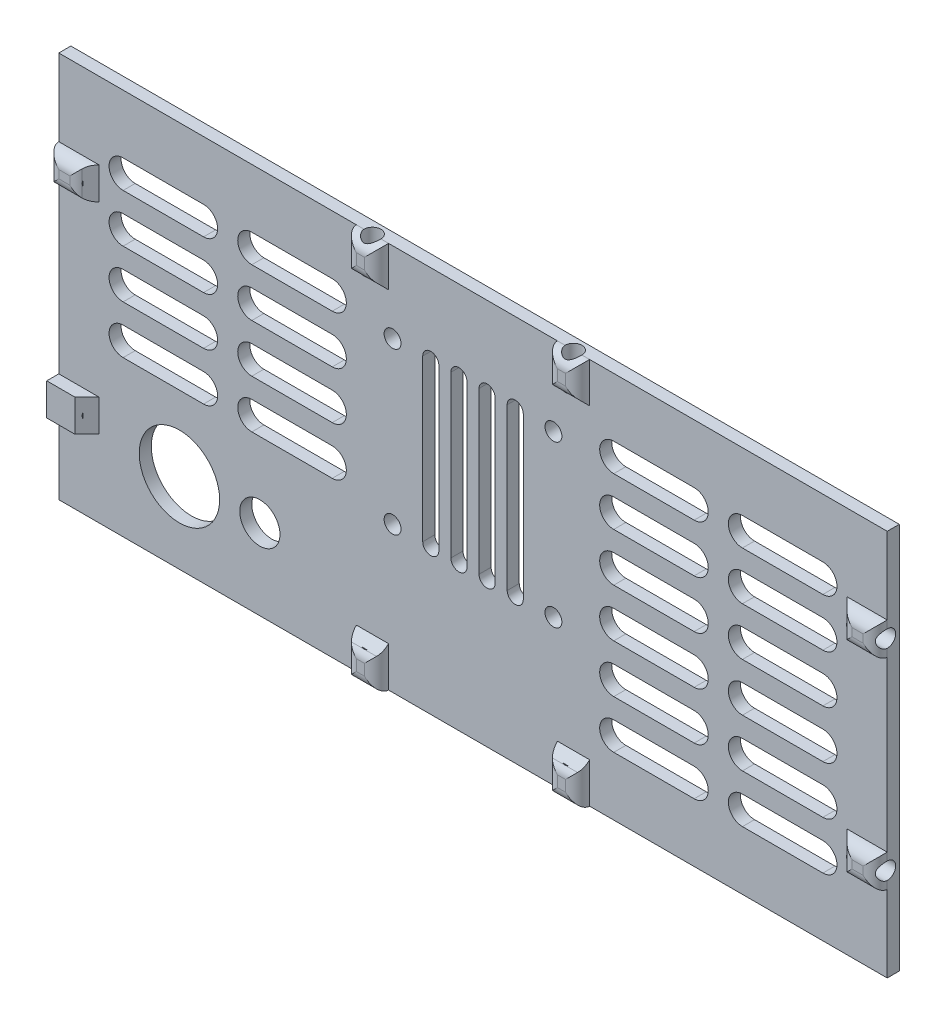
SolidWorks part; units mm, degrees
ref_plane "Front Plane" through (0, 0, 0) normal (1, 0, 0) x (0, 1, 0)
ref_plane "Top Plane" through (0, 0, 0) normal (0, 0, 1) x (0, 1, 0)
ref_plane "Right Plane" through (0, 0, 0) normal (0, 1, 0) x (-1, 0, 0)
sketch "Sketch1" plane through (0, 0, 0) normal (0, 0, 1) x (0, 1, 0)
  line L0 (36.2019, 113.5) -> (76.2019, 113.5) construction
  line L1 (0, 0) -> (96.2019, 0)
  line L2 (0, 0) -> (0, 206)
  line L3 (0, 206) -> (96.2019, 206)
  line L4 (96.2019, 0) -> (96.2019, 206)
  line L5 (36.2019, 115.5) -> (76.2019, 115.5)
  line L6 (36.2019, 111.5) -> (76.2019, 111.5)
  line L7 (36.2019, 106.5) -> (76.2019, 106.5) construction
  line L8 (36.2019, 108.5) -> (76.2019, 108.5)
  line L9 (36.2019, 104.5) -> (76.2019, 104.5)
  line L10 (36.2019, 99.5) -> (76.2019, 99.5) construction
  line L11 (36.2019, 101.5) -> (76.2019, 101.5)
  line L12 (36.2019, 97.5) -> (76.2019, 97.5)
  line L13 (36.2019, 92.5) -> (76.2019, 92.5) construction
  line L14 (36.2019, 94.5) -> (76.2019, 94.5)
  line L15 (36.2019, 90.5) -> (76.2019, 90.5)
  line L16 (6, 200) -> (90.2019, 200) construction
  line L17 (90.2019, 6) -> (90.2019, 200) construction
  line L18 (6, 6) -> (90.2019, 6) construction
  line L19 (6, 6) -> (6, 200) construction
  line L20 (6.101, 68) -> (6.101, 48) construction
  line L21 (9.601, 68) -> (9.601, 48) construction
  line L22 (96.2019, 103) -> (0, 103) construction
  line L23 (2.601, 68) -> (2.601, 48) construction
  line L24 (18.101, 68) -> (18.101, 48) construction
  line L25 (21.601, 68) -> (21.601, 48)
  line L26 (14.601, 68) -> (14.601, 48)
  line L27 (30.1009, 68) -> (30.1009, 48) construction
  line L28 (33.6009, 68) -> (33.601, 48)
  line L29 (26.6009, 68) -> (26.6009, 48)
  line L30 (42.101, 68) -> (42.1009, 48) construction
  line L31 (45.601, 68) -> (45.601, 48)
  line L32 (38.601, 68) -> (38.601, 48)
  line L33 (54.1009, 68) -> (54.1009, 48) construction
  line L34 (57.6009, 68) -> (57.6009, 48)
  line L35 (50.6009, 68) -> (50.6009, 48)
  line L36 (66.1009, 68) -> (66.1009, 48) construction
  line L37 (69.6009, 68) -> (69.6009, 48)
  line L38 (62.6009, 68) -> (62.6009, 48)
  line L39 (78.1009, 68) -> (78.1009, 48) construction
  line L40 (81.6009, 68) -> (81.6009, 48)
  line L41 (74.6009, 68) -> (74.6009, 48)
  line L42 (90.1009, 68) -> (90.1009, 48) construction
  line L43 (93.6009, 68) -> (93.6009, 48) construction
  line L44 (86.6009, 68) -> (86.6009, 48) construction
  line L45 (48.1009, 200) -> (48.1009, 6) construction
  line L46 (6, 42) -> (90.2019, 42) construction
  line L47 (6.101, 16) -> (6.101, 36) construction
  line L48 (9.601, 16) -> (9.601, 36) construction
  line L49 (2.601, 16) -> (2.601, 36) construction
  line L50 (18.101, 16) -> (18.101, 36) construction
  line L51 (21.601, 16) -> (21.601, 36)
  line L52 (14.601, 16) -> (14.601, 36)
  line L53 (30.1009, 16) -> (30.1009, 36) construction
  line L54 (33.6009, 16) -> (33.601, 36)
  line L55 (26.6009, 16) -> (26.6009, 36)
  line L56 (42.101, 16) -> (42.1009, 36) construction
  line L57 (45.601, 16) -> (45.601, 36)
  line L58 (38.601, 16) -> (38.601, 36)
  line L59 (54.1009, 16) -> (54.1009, 36) construction
  line L60 (57.6009, 16) -> (57.6009, 36)
  line L61 (50.6009, 16) -> (50.6009, 36)
  line L62 (66.1009, 16) -> (66.1009, 36) construction
  line L63 (69.6009, 16) -> (69.6009, 36)
  line L64 (62.6009, 16) -> (62.6009, 36)
  line L65 (78.1009, 16) -> (78.1009, 36) construction
  line L66 (81.6009, 16) -> (81.6009, 36)
  line L67 (74.6009, 16) -> (74.6009, 36)
  line L68 (90.1009, 16) -> (90.1009, 36) construction
  line L69 (93.6009, 16) -> (93.6009, 36) construction
  line L70 (86.6009, 16) -> (86.6009, 36) construction
  line L71 (6.101, 138) -> (6.101, 158) construction
  line L72 (9.601, 138) -> (9.601, 158) construction
  line L73 (2.601, 138) -> (2.601, 158) construction
  line L74 (18.101, 138) -> (18.101, 158) construction
  line L75 (21.601, 138) -> (21.601, 158) construction
  line L76 (14.601, 138) -> (14.601, 158) construction
  line L77 (30.1009, 138) -> (30.1009, 158) construction
  line L78 (33.6009, 138) -> (33.601, 158) construction
  line L79 (26.6009, 138) -> (26.6009, 158) construction
  line L80 (42.101, 138) -> (42.1009, 158) construction
  line L81 (45.601, 138) -> (45.601, 158)
  line L82 (38.601, 138) -> (38.601, 158)
  line L83 (54.1009, 138) -> (54.1009, 158) construction
  line L84 (57.6009, 138) -> (57.6009, 158)
  line L85 (50.6009, 138) -> (50.6009, 158)
  line L86 (66.1009, 138) -> (66.1009, 158) construction
  line L87 (69.6009, 138) -> (69.6009, 158)
  line L88 (62.6009, 138) -> (62.6009, 158)
  line L89 (78.1009, 138) -> (78.1009, 158) construction
  line L90 (81.6009, 138) -> (81.6009, 158)
  line L91 (74.6009, 138) -> (74.6009, 158)
  line L92 (90.1009, 138) -> (90.1009, 158) construction
  line L93 (93.6009, 138) -> (93.6009, 158) construction
  line L94 (86.6009, 138) -> (86.6009, 158) construction
  line L95 (6.101, 190) -> (6.101, 170) construction
  line L96 (9.601, 190) -> (9.601, 170) construction
  line L97 (2.601, 190) -> (2.601, 170) construction
  line L98 (18.101, 190) -> (18.101, 170) construction
  line L99 (21.601, 190) -> (21.601, 170) construction
  line L100 (14.601, 190) -> (14.601, 170) construction
  line L101 (30.1009, 190) -> (30.1009, 170) construction
  line L102 (33.6009, 190) -> (33.601, 170) construction
  line L103 (26.6009, 190) -> (26.6009, 170) construction
  line L104 (42.101, 190) -> (42.1009, 170) construction
  line L105 (45.601, 190) -> (45.601, 170)
  line L106 (38.601, 190) -> (38.601, 170)
  line L107 (54.1009, 190) -> (54.1009, 170) construction
  line L108 (57.6009, 190) -> (57.6009, 170)
  line L109 (50.6009, 190) -> (50.6009, 170)
  line L110 (66.1009, 190) -> (66.1009, 170) construction
  line L111 (69.6009, 190) -> (69.6009, 170)
  line L112 (62.6009, 190) -> (62.6009, 170)
  line L113 (78.1009, 190) -> (78.1009, 170) construction
  line L114 (81.6009, 190) -> (81.6009, 170)
  line L115 (74.6009, 190) -> (74.6009, 170)
  line L116 (90.1009, 190) -> (90.1009, 170) construction
  line L117 (93.6009, 190) -> (93.6009, 170) construction
  line L118 (86.6009, 190) -> (86.6009, 170) construction
  arc A0 (36.2019, 115.5) -> (36.2019, 111.5) centre (36.2019, 113.5) ccw
  arc A1 (76.2019, 111.5) -> (76.2019, 115.5) centre (76.2019, 113.5) ccw
  arc A2 (36.2019, 108.5) -> (36.2019, 104.5) centre (36.2019, 106.5) ccw
  arc A3 (76.2019, 104.5) -> (76.2019, 108.5) centre (76.2019, 106.5) ccw
  arc A4 (36.2019, 101.5) -> (36.2019, 97.5) centre (36.2019, 99.5) ccw
  arc A5 (76.2019, 97.5) -> (76.2019, 101.5) centre (76.2019, 99.5) ccw
  arc A6 (36.2019, 94.5) -> (36.2019, 90.5) centre (36.2019, 92.5) ccw
  arc A7 (76.2019, 90.5) -> (76.2019, 94.5) centre (76.2019, 92.5) ccw
  circle A8 centre (36.2019, 123) radius 2.1
  circle A9 centre (76.2019, 123) radius 2.1
  circle A10 centre (36.2019, 83) radius 2.1
  circle A11 centre (76.2019, 83) radius 2.1
  circle A12 centre (20, 176) radius 10
  circle A13 centre (20, 156) radius 5
  arc A14 (9.601, 68) -> (2.601, 68) centre (6.101, 68) ccw construction
  arc A15 (2.601, 48) -> (9.601, 48) centre (6.101, 48) ccw construction
  arc A16 (21.601, 68) -> (14.601, 68) centre (18.101, 68) ccw
  arc A17 (14.601, 48) -> (21.601, 48) centre (18.101, 48) ccw
  arc A18 (33.6009, 68) -> (26.6009, 68) centre (30.1009, 68) ccw
  arc A19 (26.6009, 48) -> (33.601, 48) centre (30.1009, 48) ccw
  arc A20 (45.601, 68) -> (38.601, 68) centre (42.101, 68) ccw
  arc A21 (38.601, 48) -> (45.601, 48) centre (42.1009, 48) ccw
  arc A22 (57.6009, 68) -> (50.6009, 68) centre (54.1009, 68) ccw
  arc A23 (50.6009, 48) -> (57.6009, 48) centre (54.1009, 48) ccw
  arc A24 (69.6009, 68) -> (62.6009, 68) centre (66.1009, 68) ccw
  arc A25 (62.6009, 48) -> (69.6009, 48) centre (66.1009, 48) ccw
  arc A26 (81.6009, 68) -> (74.6009, 68) centre (78.1009, 68) ccw
  arc A27 (74.6009, 48) -> (81.6009, 48) centre (78.1009, 48) ccw
  arc A28 (93.6009, 68) -> (86.6009, 68) centre (90.1009, 68) ccw construction
  arc A29 (86.6009, 48) -> (93.6009, 48) centre (90.1009, 48) ccw construction
  arc A30 (9.601, 16) -> (2.601, 16) centre (6.101, 16) cw construction
  arc A31 (2.601, 36) -> (9.601, 36) centre (6.101, 36) cw construction
  arc A32 (21.601, 16) -> (14.601, 16) centre (18.101, 16) cw
  arc A33 (14.601, 36) -> (21.601, 36) centre (18.101, 36) cw
  arc A34 (33.6009, 16) -> (26.6009, 16) centre (30.1009, 16) cw
  arc A35 (26.6009, 36) -> (33.601, 36) centre (30.1009, 36) cw
  arc A36 (45.601, 16) -> (38.601, 16) centre (42.101, 16) cw
  arc A37 (38.601, 36) -> (45.601, 36) centre (42.1009, 36) cw
  arc A38 (57.6009, 16) -> (50.6009, 16) centre (54.1009, 16) cw
  arc A39 (50.6009, 36) -> (57.6009, 36) centre (54.1009, 36) cw
  arc A40 (69.6009, 16) -> (62.6009, 16) centre (66.1009, 16) cw
  arc A41 (62.6009, 36) -> (69.6009, 36) centre (66.1009, 36) cw
  arc A42 (81.6009, 16) -> (74.6009, 16) centre (78.1009, 16) cw
  arc A43 (74.6009, 36) -> (81.6009, 36) centre (78.1009, 36) cw
  arc A44 (93.6009, 16) -> (86.6009, 16) centre (90.1009, 16) cw construction
  arc A45 (86.6009, 36) -> (93.6009, 36) centre (90.1009, 36) cw construction
  arc A46 (9.601, 138) -> (2.601, 138) centre (6.101, 138) cw construction
  arc A47 (2.601, 158) -> (9.601, 158) centre (6.101, 158) cw construction
  arc A48 (21.601, 138) -> (14.601, 138) centre (18.101, 138) cw construction
  arc A49 (14.601, 158) -> (21.601, 158) centre (18.101, 158) cw construction
  arc A50 (33.6009, 138) -> (26.6009, 138) centre (30.1009, 138) cw construction
  arc A51 (26.6009, 158) -> (33.601, 158) centre (30.1009, 158) cw construction
  arc A52 (45.601, 138) -> (38.601, 138) centre (42.101, 138) cw
  arc A53 (38.601, 158) -> (45.601, 158) centre (42.1009, 158) cw
  arc A54 (57.6009, 138) -> (50.6009, 138) centre (54.1009, 138) cw
  arc A55 (50.6009, 158) -> (57.6009, 158) centre (54.1009, 158) cw
  arc A56 (69.6009, 138) -> (62.6009, 138) centre (66.1009, 138) cw
  arc A57 (62.6009, 158) -> (69.6009, 158) centre (66.1009, 158) cw
  arc A58 (81.6009, 138) -> (74.6009, 138) centre (78.1009, 138) cw
  arc A59 (74.6009, 158) -> (81.6009, 158) centre (78.1009, 158) cw
  arc A60 (93.6009, 138) -> (86.6009, 138) centre (90.1009, 138) cw construction
  arc A61 (86.6009, 158) -> (93.6009, 158) centre (90.1009, 158) cw construction
  arc A62 (9.601, 190) -> (2.601, 190) centre (6.101, 190) ccw construction
  arc A63 (2.601, 170) -> (9.601, 170) centre (6.101, 170) ccw construction
  arc A64 (21.601, 190) -> (14.601, 190) centre (18.101, 190) ccw construction
  arc A65 (14.601, 170) -> (21.601, 170) centre (18.101, 170) ccw construction
  arc A66 (33.6009, 190) -> (26.6009, 190) centre (30.1009, 190) ccw construction
  arc A67 (26.6009, 170) -> (33.601, 170) centre (30.1009, 170) ccw construction
  arc A68 (45.601, 190) -> (38.601, 190) centre (42.101, 190) ccw
  arc A69 (38.601, 170) -> (45.601, 170) centre (42.1009, 170) ccw
  arc A70 (57.6009, 190) -> (50.6009, 190) centre (54.1009, 190) ccw
  arc A71 (50.6009, 170) -> (57.6009, 170) centre (54.1009, 170) ccw
  arc A72 (69.6009, 190) -> (62.6009, 190) centre (66.1009, 190) ccw
  arc A73 (62.6009, 170) -> (69.6009, 170) centre (66.1009, 170) ccw
  arc A74 (81.6009, 190) -> (74.6009, 190) centre (78.1009, 190) ccw
  arc A75 (74.6009, 170) -> (81.6009, 170) centre (78.1009, 170) ccw
  arc A76 (93.6009, 190) -> (86.6009, 190) centre (90.1009, 190) ccw construction
  arc A77 (86.6009, 170) -> (93.6009, 170) centre (90.1009, 170) ccw construction
  point P7 (56.2019, 113.5)
  point P12 (56.2019, 106.5)
  point P19 (56.2019, 99.5)
  point P26 (56.2019, 92.5)
  point P39 (6.101, 58)
  point P40 (90.1952, 103)
  point P57 (18.101, 58)
  point P65 (30.1009, 58)
  point P72 (42.101, 58)
  point P81 (54.1009, 58)
  point P88 (66.1009, 58)
  point P95 (78.1009, 58)
  point P102 (90.1009, 58)
  point P116 (6.101, 26)
  point P123 (18.101, 26)
  point P130 (30.1009, 26)
  point P137 (42.101, 26)
  point P144 (54.1009, 26)
  point P151 (66.1009, 26)
  point P158 (78.1009, 26)
  point P165 (90.1009, 26)
  point P172 (6.101, 148)
  point P179 (18.101, 148)
  point P186 (30.1009, 148)
  point P193 (42.101, 148)
  point P200 (54.1009, 148)
  point P207 (66.1009, 148)
  point P214 (78.1009, 148)
  point P221 (90.1009, 148)
  point P228 (6.101, 180)
  point P235 (18.101, 180)
  point P242 (30.1009, 180)
  point P249 (42.101, 180)
  point P256 (54.1009, 180)
  point P263 (66.1009, 180)
  point P270 (78.1009, 180)
  point P277 (90.1009, 180)
  dimension "D9" = 4.2
  dimension "D13" = 20
  dimension "D14" = 10
  dimension "D1" = 96.2019
  dimension "D2" = 206
  dimension "D5" = 3
  dimension "D7" = 4
  dimension "D11" = 20
  dimension "D12" = 40
  dimension "D10" = 40
  dimension "D6" = 3
  dimension "D15" = 20
  dimension "D16" = 30
  dimension "D17" = 20
  dimension "D19" = 7
  dimension "D20" = 20
  dimension "D21" = 5
  dimension "D22" = 6
  dimension "D23" = 10
  dimension "D3" = 6
  dimension "D18" = 8
extrude "Boss-Extrude1" add sketch "Sketch1" along normal blind 3
sketch "Sketch2" plane through (0, 0, 0) normal (0, -1, 0) x (1, 0, 0)
  line L0 (-128, 6) -> (-128, 0) construction
  line L1 (-132, 6) -> (-124, 6)
  line L2 (-132, 6) -> (-132, 0)
  line L3 (-132, 6) -> (-132, 0)
  line L4 (-124, 6) -> (-124, 0)
  line L5 (-103, 3) -> (-103, 0) construction
  line L6 (-206, 3) -> (0, 3) construction
  line L7 (-206, 0) -> (0, 0) construction
  line L8 (-132, 0) -> (-124, 0)
  line L9 (-124, 6) -> (-124, 0)
  line L10 (-78, 6) -> (-78, 0) construction
  line L11 (-82, 6) -> (-82, 0)
  line L12 (-74, 0) -> (-82, 0)
  line L13 (-82, 6) -> (-82, 0)
  line L14 (-74, 6) -> (-74, 0)
  line L15 (-74, 6) -> (-74, 0)
  line L16 (-74, 6) -> (-82, 6)
  circle A0 centre (-128, 3) radius 2.1
  circle A2 centre (-78, 3) radius 2.1
  point P13 (0, 0)
  point P14 (0, 0)
  point P15 (-142.1835, 6)
  line M3 (-206, 0) -> (0, 0)
  line M5 (0, 3) -> (-206, 3)
  dimension "D3" = 6
  dimension "D1" = 4.2
  dimension "D4" = 25
extrude "Boss-Extrude6" add sketch "Sketch2<4>" against normal blind 10 contours A2 L14 L16 L11 M5 | A2 L11 L14 M5 M3 | A2 M5 | A2 M5 | A0 L4 L1 L2 M5 | A0 L2 L4 M5 M3 | A0 M5 | A0 M5 region at (-128, 0, 5.9146) region at (-131.05, 0, 2.9146) region at (-128, 0, 2.1087) region at (-128, 0, 3.8913) region at (-81.05, 0, 2.9146) region at (-81.9146, 0, 4.5) region at (-78, 0, 2.1087) region at (-78, 0, 3.8913)
sketch "Sketch2<4>" plane through (0, 0, 0) normal (0, -1, 0) x (1, 0, 0) same geometry as "Sketch2"
extrude "Boss-Extrude7" add sketch "Sketch2" along normal blind 10 from surface contours A0 L4 L1 L2 M5 | A0 L2 L4 M5 M3 | A0 M5 | A0 M5 | A2 L11 L14 M5 M3 | A2 M5 | A2 L14 L16 L11 M5 | A2 M5 region at (-128, 0, 5.9146) region at (-131.05, 0, 2.9146) region at (-128, 0, 2.1087) region at (-128, 0, 3.8913) region at (-81.05, 0, 2.9146) region at (-81.9146, 0, 4.5) region at (-78, 0, 2.1087) region at (-78, 0, 3.8913) starting at face at (-103, 96.2019, 1.5)
sketch "Sketch3" plane through (0, 0, 0) normal (1, 0, 0) x (0, 1, 0)
  line L1 (23.1009, 6) -> (23.1009, 0) construction
  line L4 (0, 3) -> (96.2019, 3) construction
  line L5 (48.1009, 3) -> (48.1009, 0) construction
  line L6 (0, 0) -> (96.2019, 0) construction
  line L7 (19.1009, 6) -> (27.1009, 6)
  line L8 (19.1009, 6) -> (19.1009, 0)
  line L9 (19.1009, 0) -> (27.1009, 0)
  line L10 (27.1009, 6) -> (27.1009, 0)
  line L11 (19.1009, 6) -> (19.1009, 0)
  line L12 (27.1009, 6) -> (27.1009, 0)
  line L13 (19.1009, 6) -> (19.1009, 0)
  line L14 (27.1009, 6) -> (27.1009, 0)
  line L15 (19.1009, 6) -> (19.1009, 0)
  line L16 (27.1009, 6) -> (27.1009, 0)
  line L17 (69.1009, 6) -> (69.1009, 0)
  line L18 (77.1009, 0) -> (69.1009, 0)
  line L19 (77.1009, 6) -> (77.1009, 0)
  line L20 (77.1009, 6) -> (69.1009, 6)
  circle A0 centre (23.1009, 3) radius 2.1
  circle A2 centre (73.1009, 3) radius 2.1
  line M3 (0, 0) -> (96.2019, 0)
  line M5 (96.2019, 3) -> (0, 3)
  dimension "D1" = 4.2
  dimension "D4" = 25
  dimension "D2" = 6
  dimension "D3" = 8
extrude "Boss-Extrude3" add sketch "Sketch3<3>" against normal blind 10 contours A2 L19 L20 L17 M5 | A2 L17 L19 M5 M3 | A2 M5 | A2 M5 | A0 L10 L7 L8 M5 | A0 L8 L10 M5 M3 | A0 M5 | A0 M5 region at (0, 23.1009, 5.9146) region at (0, 20.051, 2.9146) region at (0, 23.1009, 2.1087) region at (0, 23.1009, 3.8913) region at (0, 70.051, 2.9146) region at (0, 69.1864, 4.5) region at (0, 73.1009, 2.1087) region at (0, 73.1009, 3.8913)
sketch "Sketch3<3>" plane through (0, 0, 0) normal (1, 0, 0) x (0, 1, 0) same geometry as "Sketch3"
extrude "Boss-Extrude4" add sketch "Sketch3" along normal blind 10 from surface contours A0 L10 L7 L8 M5 | A0 L8 L10 M5 M3 | A0 M5 | A0 M5 | A2 L19 L20 L17 M5 | A2 L17 L19 M5 M3 | A2 M5 | A2 M5 region at (0, 23.1009, 5.9146) region at (0, 20.051, 2.9146) region at (0, 23.1009, 2.1087) region at (0, 23.1009, 3.8913) region at (0, 70.051, 2.9146) region at (0, 69.1864, 4.5) region at (0, 73.1009, 2.1087) region at (0, 73.1009, 3.8913) starting at face at (-206, 48.1009, 1.5)
extrude "Cut-Extrude4" cut sketch "Sketch3<2>" along normal blind 8 from surface contours A0 M5 | A0 M5 | A2 M5 | A2 M5 region at (0, 23.1009, 2.1087) region at (0, 23.1009, 3.8913) region at (0, 73.1009, 2.1087) region at (0, 73.1009, 3.8913) starting at face at (-206, 48.1009, 3.5)
sketch "Sketch3<2>" plane through (0, 0, 0) normal (1, 0, 0) x (0, 1, 0) same geometry as "Sketch3"
extrude "Cut-Extrude5" cut sketch "Sketch3<5>" against normal blind 8 contours A0 M5 | A0 M5 | A2 M5 | A2 M5 region at (0, 23.1009, 2.1087) region at (0, 23.1009, 3.8913) region at (0, 73.1009, 2.1087) region at (0, 73.1009, 3.8913)
sketch "Sketch3<5>" plane through (0, 0, 0) normal (1, 0, 0) x (0, 1, 0) same geometry as "Sketch3"
extrude "Cut-Extrude6" cut sketch "Sketch2<6>" against normal blind 8 contours A2 M5 | A2 M5 | A0 M5 | A0 M5 region at (-128, 0, 2.1087) region at (-128, 0, 3.8913) region at (-78, 0, 2.1087) region at (-78, 0, 3.8913)
sketch "Sketch2<6>" plane through (0, 0, 0) normal (0, -1, 0) x (1, 0, 0) same geometry as "Sketch2"
extrude "Cut-Extrude7" cut sketch "Sketch2<7>" along normal blind 8 from surface contours A2 M5 | A2 M5 | A0 M5 | A0 M5 region at (-128, 0, 2.1087) region at (-128, 0, 3.8913) region at (-78, 0, 2.1087) region at (-78, 0, 3.8913) starting at face at (-103, 96.2019, 3.5)
sketch "Sketch2<7>" plane through (0, 0, 0) normal (0, -1, 0) x (1, 0, 0) same geometry as "Sketch2"
chamfer "Chamfer1" distance 3 angle 45 8 edges at (-78, 86.2019, 6) (-78, 10, 6) (-128, 10, 6) (-128, 86.2019, 6) (-10, 73.1009, 6) (-10, 23.1009, 6) (-196, 73.1009, 6) (-196, 23.1009, 6)
fillet "Fillet1" radius 3 28 edges at (-78, 96.2019, 6) (-74, 92.7019, 6) (-78, 89.2019, 6) (-82, 92.7019, 6) (-128, 96.2019, 6) (-124, 92.7019, 6) (-128, 89.2019, 6) (-132, 92.7019, 6) (-206, 73.1009, 6) (-202.5, 77.1009, 6) (-199, 73.1009, 6) (-202.5, 69.1009, 6) (-128, 0, 6) (-132, 3.5, 6) (-128, 7, 6) (-124, 3.5, 6) (-78, 0, 6) (-82, 3.5, 6) (-78, 7, 6) (-74, 3.5, 6) (0, 73.1009, 6) (-3.5, 69.1009, 6) (-7, 73.1009, 6) (-3.5, 77.1009, 6) (0, 23.1009, 6) (-3.5, 19.1009, 6) (-7, 23.1009, 6) (-3.5, 27.1009, 6)
equation "\"MotorDriverLength\"= 60mm"
equation "\"MotorLength\"= 60"
equation "\"MotorDriverWidth\"=44"
equation "\"MotorWidth\"= 37"
equation "\"InnerWallThickness\"=3"
equation "\"BatteryWidth\"= 60"
equation "\"OuterWallThickness\" = 6"
equation "\"CompartmentHeight\"=37"
equation "\"CompartmentWidth\"= \"MotorDriverLength\""
equation "\"MotorDiameter\"=37"
equation "\"BatteryHeight\"=24.2019"
equation "\"MotorDriverHeight\"=28"
equation "\"CircuitHeight\"=30"
equation "\"FanThickness\"= 10"
equation "\"FanHeight\"=50"
equation "\"MotorShaftHole\"=12"
equation "\"BearingBore\"=4"
equation "\"MinShinWidth\"= 20"
equation "\"ShinThickness\"=10"
equation "\"PivotDistance\"=30"
equation "\"ThighLength\"= 200"
equation "\"KneeLength\" =20"
equation "\"HipBore\"=27"
equation "\"ThighThickness\"=20"
equation "\"MaxBending\"=135"
equation "\"MaxStretchingAngle\"= 140"
equation "\"ThighJointDistance\"=157.485"
equation "\"ShinLength\"=120"
equation "\"BearingDiameter\"= 10"
equation "\"CircuitLength\"=50"
equation "\"ChessisInnerWidth\"= \"OuterWallThickness\" * 2 + \"MotorDriverLength\" + \"MotorDiameter\" + \"InnerWallThickness\" * 3 + \"CircuitLength\""
equation "\"ChessisHeight\"= \"BatteryHeight\" + 10 + \"InnerWallThickness\" + \"MotorDiameter\" + 10 + \"OuterWallThickness\" * 2"
equation "\"D1@Sketch1\"=\"ChessisHeight\""
equation "\"ChassisWidth\"= \"MotorDriverWidth\"*4+30"
equation "\"D2@Sketch1\"=\"ChassisWidth\""
equation "\"D1@Boss-Extrude1\"=3"
equation "\"D3@Sketch2\"=\"OuterWallThickness\""
equation "\"D2@Sketch3\"=\"OuterWallThickness\""
